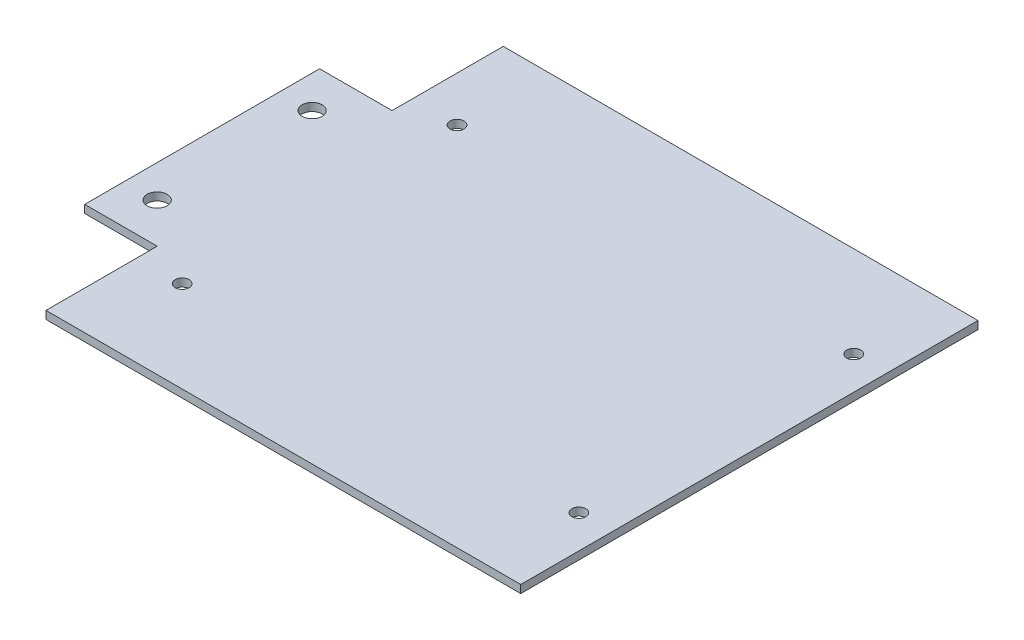
SolidWorks part; units mm, degrees
note: The reader was unsure of these and kept them because the rebuilt part matched: thickness of "Base-Flange1", "Sheet-Metal1".
ref_plane "Front Plane" through (0, 0, 0) normal (0, 0, 1) x (1, 0, 0)
ref_plane "Top Plane" through (0, 0, 0) normal (0, 1, 0) x (1, 0, 0)
ref_plane "Right Plane" through (0, 0, 0) normal (1, 0, 0) x (0, 0, -1)
sketch "Sketch1" plane through (0, 0, 0) normal (0, 1, 0) x (1, 0, 0)
  line L1 (-95, 91.5) -> (95, 91.5)
  line L3 (-95, -91.5) -> (95, -91.5)
  line L4 (95, 91.5) -> (95, -91.5)
  line L5 (0, -91.5) -> (0, 91.5) construction
  line L6 (-95, 0) -> (95, 0) construction
  line L7 (-77, -55.0037) -> (81.76, -55.0037) construction
  line L8 (81.76, -55.0037) -> (81.76, 55.0037) construction
  line L9 (81.76, 55.0037) -> (-77, 55.0037) construction
  line L10 (-77, 55.0037) -> (-77, -55.0037) construction
  line L11 (-95, 91.5) -> (-95, 47)
  line L12 (-95, 47) -> (-124, 47)
  line L13 (-124, 47) -> (-124, -47)
  line L14 (-124, -47) -> (-95, -47)
  line L15 (-95, -47) -> (-95, -91.5)
  line L16 (-111, 31) -> (-111, -31) construction
  circle A0 centre (-77, 55.0037) radius 2.8
  circle A1 centre (-77, -55.0037) radius 2.8
  circle A2 centre (81.76, -55.0037) radius 2.8
  circle A3 centre (81.76, 55.0037) radius 2.8
  circle A4 centre (-111, 31) radius 4
  circle A6 centre (-111, -31) radius 4
  arc A7 (-83, 52.2097) -> (-83, 57.7977) centre (-83, 55.0037) ccw construction
  arc A8 (-83, 52.2097) -> (-83, 57.7977) centre (-83, 55.0037) ccw construction
  arc A9 (72.9629, -55.0037) -> (75.7569, -57.7977) centre (75.7569, -55.0037) ccw construction
  arc A10 (72.9629, 55.0037) -> (75.7569, 52.2097) centre (75.7569, 55.0037) ccw construction
  arc A11 (72.9629, -55.0037) -> (75.7569, -57.7977) centre (75.7569, -55.0037) ccw construction
  arc A12 (72.9629, 55.0037) -> (75.7569, 52.2097) centre (75.7569, 55.0037) ccw construction
  point P0 (0, 0)
  point P12 (-111, 0)
  point P16 (81.76, 0)
  dimension "D1" = 158.76
  dimension "D5" = 5.6
  dimension "D9" = 8
  dimension "D11" = 13
  dimension "D2" = 183
  dimension "D3" = 110.0074
  dimension "D4" = 29
  dimension "D6" = 94
  dimension "D7" = 190
  dimension "D8" = 18
  dimension "D10" = 62
base flange "Base-Flange1" sketch "Sketch1" thickness 3.17 reverse thickness direction no parameters "D1"=2
sketch "Bend-Lines1" [suppressed] plane through (0, 0, 0) normal (0, 1, 0) x (1, 0, 0)
sketch "Bounding-Box1" [suppressed] plane through (0, 0, 0) normal (0, 1, 0) x (1, 0, 0)
sheet metal parameters "Sheet-Metal1" thickness 3.17 parameters "D1"=2
flat pattern "Flat-Pattern1" [suppressed]
sketch "Bend-Lines2" plane through (0, 0, 0) normal (0, 1, 0) x (1, 0, 0)
sketch3d "Bounding-Box2" [suppressed]
  line L0 (95, -91.5, 0) -> (-124, -91.5, 0) construction
  line L1 (95, 91.5, 0) -> (-124, 91.5, 0) construction
  line L2 (95, -91.5, 0) -> (95, 91.5, 0) construction
  line L3 (-124, -91.5, 0) -> (-124, 91.5, 0) construction
